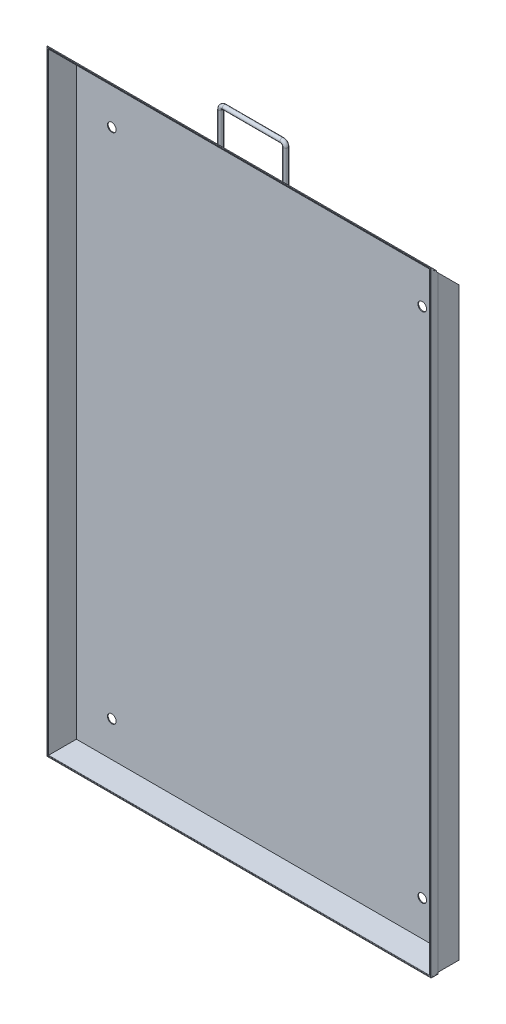
SolidWorks part; units mm, degrees
ref_plane "Front Plane" through (0, 0, 0) normal (0, 0, 1) x (1, 0, 0)
ref_plane "Top Plane" through (0, 0, 0) normal (0, 1, 0) x (1, 0, 0)
ref_plane "Right Plane" through (0, 0, 0) normal (1, 0, 0) x (0, 0, -1)
ref_plane "Plane1" through (0, 0, 0) normal (1, 0, 0) x (0, 0, -1)
sketch "Sketch2" plane through (0, 0, 0) normal (1, 0, 0) x (0, 0, -1)
  line L1 (0, 20) -> (-40, 20)
  line L2 (0, 20) -> (0, 830)
  line L3 (-40, 868.5858) -> (-1, 829.5858)
  line L4 (-1, 21) -> (-1, 829.5858)
  line L6 (-40, 870) -> (0, 830)
  line L7 (-1, 21) -> (-40, 21)
  line L8 (-40, 870) -> (-40, 868.5858)
  line L9 (-40.7071, 869.2929) -> (-1, 829.5858) construction
  line L10 (-40, 21) -> (-40, 20)
  dimension "D1" = 850
  dimension "D2" = 40
  dimension "D3" = 1
extrude "Boss-Extrude1" add sketch "Sketch2" along normal mid plane 530
sketch "Sketch3" plane through (265, 0, 0) normal (1, 0, 0) x (0, 0, -1)
  line L0 (-40, 870) -> (0, 830)
  line L1 (0, 830) -> (0, 20)
  line L2 (0, 20) -> (-40, 20)
  line L3 (-40, 20) -> (-40, 870)
extrude "Boss-Extrude2" add sketch "Sketch3" against normal blind 1
sketch "Sketch4" plane through (-265, 0, 0) normal (-1, 0, 0) x (0, 0, 1)
  line L4 (40, 870) -> (0, 830)
  line L5 (0, 830) -> (0, 20)
  line L6 (0, 20) -> (40, 20)
  line L7 (40, 20) -> (40, 870)
  line L8 (40, 870) -> (0, 830)
  line L9 (0, 830) -> (0, 20)
  line L10 (0, 20) -> (40, 20)
  line L11 (40, 20) -> (40, 870)
  dimension "D1" = 0
extrude "Boss-Extrude3" add sketch "Sketch4" against normal blind 1
sketch "Sketch5" plane through (0, 0, 1) normal (0, 0, 1) x (1, 0, 0)
  line L0 (-265, 870) -> (-265, 20) construction
  line L1 (265, 20) -> (-265, 20) construction
  line L2 (264, 829.5858) -> (-264, 829.5858) construction
  line L3 (265, 870) -> (265, 20) construction
  circle A0 centre (215, 779.5858) radius 6
  circle A1 centre (215, 70) radius 6
  circle A2 centre (-215, 779.5858) radius 6
  circle A3 centre (-215, 70) radius 6
  dimension "D1" = 12
  dimension "D2" = 12
  dimension "D3" = 12
  dimension "D4" = 12
  dimension "D5" = 50
  dimension "D6" = 50
  dimension "D7" = 50
  dimension "D8" = 50
  dimension "D9" = 50
  dimension "D10" = 50
  dimension "D11" = 50
  dimension "D12" = 50
extrude "Cut-Extrude1" cut sketch "Sketch5" against normal blind 1
ref_plane "Plane2" through (0, 891, 0) normal (0, 1, 0) x (1, 0, 0)
sketch "Sketch6" plane through (0, 891, 0) normal (0, 1, 0) x (1, 0, 0)
  line L0 (-265, -20) -> (265, -20) construction
  line L1 (-265, 0) -> (-265, -40) construction
  line L2 (265, 0) -> (265, -40) construction
  line L3 (0, -20) -> (0, 8.8563) construction
  circle A0 centre (-45, -20) radius 3
  circle A1 centre (45, -20) radius 3
  dimension "D1" = 6
  dimension "D2" = 45
extrude "Boss-Extrude5" add sketch "Sketch6" against normal up to surface (38 mm away) up to face at (0, 850, 20)
ref_plane "Plane4" through (0, 0, 20) normal (0, 0, -1) x (-1, 0, 0)
sketch "Sketch9" plane through (0, 0, 20) normal (0, 0, -1) x (-1, 0, 0)
  line L0 (-45, 891) -> (-45, 896)
  line L1 (-42, 891) -> (-48, 891) construction
  line L2 (45, 896) -> (45, 891)
  line L3 (48, 891) -> (42, 891) construction
  line L4 (-40, 901) -> (40, 901)
  arc A0 (45, 896) -> (40, 901) centre (40, 896) ccw
  arc A1 (-45, 896) -> (-40, 901) centre (-40, 896) cw
  point P12 (-45, 901)
  dimension "D2" = 5
  dimension "D1" = 10
  dimension "D3" = 10
sketch "Sketch10" plane through (0, 891, 0) normal (0, 1, 0) x (1, 0, 0)
  circle A1 centre (45, -20) radius 3
  circle A2 centre (45, -20) radius 3
  dimension "D1" = 0
sweep "Sweep1" add profiles "Sketch10" path "Sketch9"
ref_plane "Plane5" through (265.1, 0, 0) normal (1, 0, 0) x (0, 0, -1)
sketch "Sketch13" plane through (265.1, 0, 0) normal (1, 0, 0) x (0, 0, -1)
  line L0 (-30, 20) -> (-30, 860)
  line L4 (0, 20) -> (0, 830)
  line L5 (0, 830) -> (-40, 870)
  line L6 (-40, 870) -> (-40, 20)
  line L7 (-40, 20) -> (0, 20)
  line L9 (-30, 860) -> (-40, 870)
  line L10 (-40, 870) -> (-40, 20)
  line L11 (-40, 20) -> (-30, 20)
  dimension "D2" = 10
  dimension "D1" = 0
extrude "Boss-Extrude7" add sketch "Sketch13" along normal blind 1 separate body
ref_plane "Plane6" through (-265.1, 0, 0) normal (-1, 0, 0) x (0, 0, 1)
sketch "Sketch15" plane through (-265.1, 0, 0) normal (-1, 0, 0) x (0, 0, 1)
  line L0 (30, 20) -> (30, 860)
  line L4 (0, 830) -> (0, 20)
  line L5 (0, 20) -> (40, 20)
  line L6 (40, 20) -> (40, 870)
  line L7 (40, 870) -> (0, 830)
  line L9 (30, 20) -> (40, 20)
  line L10 (40, 20) -> (40, 870)
  line L11 (40, 870) -> (30, 860)
  dimension "D2" = 10
  dimension "D1" = 0
extrude "Boss-Extrude8" add sketch "Sketch15" along normal blind 1 separate body
ref_plane "Plane7" through (0, 19.9, 0) normal (0, -1, 0) x (-1, 0, 0)
sketch "Sketch16" plane through (0, 19.9, 0) normal (0, -1, 0) x (-1, 0, 0)
  line L1 (-266.1, -40) -> (266.1, -40)
  line L2 (-266.1, -40) -> (-266.1, -30)
  line L3 (-266.1, -30) -> (266.1, -30)
  line L4 (266.1, -40) -> (266.1, -30)
extrude "Boss-Extrude9" add sketch "Sketch16" along normal blind 1 separate body
ref_plane "Plane8" through (0, 415.0707, -415.0707) normal (0, 0.7071, -0.7071) x (-1, 0, 0)
sketch "Sketch18" plane through (0, 415.0707, -415.0707) normal (0, 0.7071, -0.7071) x (-1, 0, 0)
  line L0 (266.1, 643.4672) -> (266.1, 629.325) construction
  line L1 (-266.1, 643.4672) -> (266.1, 643.4672)
  line L2 (-266.1, 643.4672) -> (-266.1, 633.4672)
  line L3 (-266.1, 633.4672) -> (266.1, 633.4672)
  line L4 (266.1, 643.4672) -> (266.1, 633.4672)
  dimension "D1" = 10
extrude "Boss-Extrude10" add sketch "Sketch18" along normal blind 1 separate body
sketch "Sketch19" plane through (0, 0, 40) normal (0, 0, 1) x (1, 0, 0)
  line L1 (-266.1, 18.9) -> (266.1, 18.9)
  line L2 (-266.1, 18.9) -> (-266.1, 870.0707)
  line L3 (-266.1, 870.0707) -> (266.1, 870.0707)
  line L4 (266.1, 18.9) -> (266.1, 870.0707)
  line L5 (264, 868.5858) -> (-264, 868.5858)
  line L6 (264, 868.5858) -> (264, 21)
  line L7 (264, 21) -> (-264, 21)
  line L8 (-264, 868.5858) -> (-264, 21)
extrude "Boss-Extrude11" add sketch "Sketch19" against normal blind 1
sketch "Sketch20" plane through (266.1, 0, 0) normal (1, 0, 0) x (0, 0, -1)
  line L0 (-39.9293, 870.0707) -> (-40, 870)
  line L1 (-40, 18.9) -> (-40, 870.0707) construction
  line L2 (-40, 870) -> (-40, 870.0707)
  line L3 (-40, 870.0707) -> (-39.9293, 870.0707)
  line L4 (-39.2222, 870.7778) -> (-39.9293, 870.0707) construction
extrude "Cut-Extrude2" cut sketch "Sketch20" against normal up to surface (532.2 mm away) up to face at (-266.1, 503.8119, 35.7258)
fillet "Fillet1" radius 0.5 8 edges at (0, 870, 40) (-266.1, 444.45, 40) (-264, 444.7929, 40) (0, 868.5858, 40) (264, 444.7929, 40) (266.1, 444.45, 40) (0, 21, 40) (0, 18.9, 40)
fillet "Fillet2" radius 0.5 1 edges at (0, 870.7778, 39.2222)
